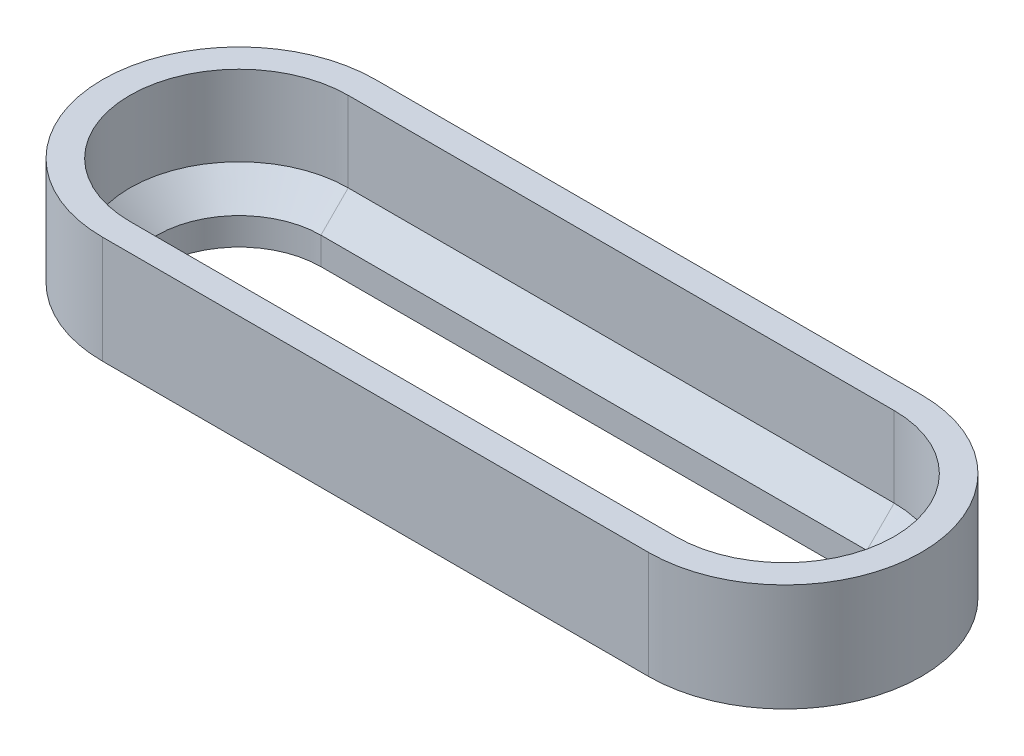
SolidWorks part; units mm, degrees
ref_plane "Front Plane" through (0, 0, 0) normal (0, 0, 1) x (1, 0, 0)
ref_plane "Top Plane" through (0, 0, 0) normal (0, 1, 0) x (1, 0, 0)
ref_plane "Right Plane" through (0, 0, 0) normal (1, 0, 0) x (0, 0, -1)
sketch "Sketch1" plane through (0, 0, 0) normal (0, 1, 0) x (1, 0, 0)
  line L1 (-25.4, -12.7) -> (25.4, -12.7)
  line L2 (-25.4, 12.7) -> (25.4, 12.7)
  line L4 (-25.4, -12.7) -> (25.4, 12.7) construction
  line L5 (-25.4, 12.7) -> (25.4, -12.7) construction
  line L6 (-38.1, 0) -> (38.1, 0) construction
  line L7 (-25.4, -10.16) -> (25.4, -10.16)
  line L8 (-25.4, 10.16) -> (25.4, 10.16)
  line L9 (0, 0) -> (0, 22.735) construction
  arc A0 (-25.4, 12.7) -> (-25.4, -12.7) centre (-25.4, 0) ccw
  arc A2 (25.4, -12.7) -> (25.4, 12.7) centre (25.4, 0) ccw
  arc A3 (-25.4, 10.16) -> (-25.4, -10.16) centre (-25.4, 0) ccw
  arc A4 (25.4, -10.16) -> (25.4, 10.16) centre (25.4, 0) ccw
  point P1 (0, 0)
  point P16 (38.1, 0)
  point P17 (40.7246, -18.7831)
  point P20 (39.8821, 2.5344)
  point P21 (50.7514, 0)
  point P22 (0, 0)
  dimension "D1" = 76.2
  dimension "D2" = 25.4
  dimension "D3" = 2.54
extrude "Boss-Extrude1" add sketch "Sketch1" along normal blind 10
sketch "Sketch3" plane through (0, 0, 0) normal (0, -1, 0) x (1, 0, 0)
  line L6 (25.4, 10.16) -> (-25.4, 10.16)
  line L7 (-25.4, -10.16) -> (25.4, -10.16)
  line L8 (-25.4, -7.62) -> (25.4, -7.62)
  line L9 (25.4, 7.62) -> (-25.4, 7.62)
  line L10 (-25.4, -7.62) -> (25.4, -7.62)
  line L11 (25.4, 7.62) -> (-25.4, 7.62)
  arc A4 (25.4, -10.16) -> (25.4, 10.16) centre (25.4, 0) ccw
  arc A5 (-25.4, 10.16) -> (-25.4, -10.16) centre (-25.4, 0) ccw
  arc A6 (25.4, -7.62) -> (25.4, 7.62) centre (25.4, 0) ccw
  arc A7 (-25.4, 7.62) -> (-25.4, -7.62) centre (-25.4, 0) ccw
  arc A8 (25.4, -7.62) -> (25.4, 7.62) centre (25.4, 0) ccw
  arc A9 (-25.4, 7.62) -> (-25.4, -7.62) centre (-25.4, 0) ccw
  dimension "D1" = 2.54
  dimension "D2" = 2.54
extrude "Boss-Extrude2" add sketch "Sketch3" along normal blind 2.54 and the other way blind 2.54
chamfer "Chamfer1" distance 2.54 angle 45 8 edges at (35.56, -2.54, 0) (0, -2.54, 10.16) (0, -2.54, -10.16) (-35.56, -2.54, 0) (0, 2.54, 7.62) (-33.02, 2.54, 0) (33.02, 2.54, 0) (0, 2.54, -7.62)
ref_plane "Plane1" through (-25.4, 0, 0) normal (-1, 0, 0) x (0, 0, 1)
ref_plane "Plane2" through (25.4, 0, 0) normal (-1, 0, 0) x (0, 0, 1)
ref_plane "Plane3" through (0, 0, 0) normal (-1, 0, 0) x (0, 0, 1)
